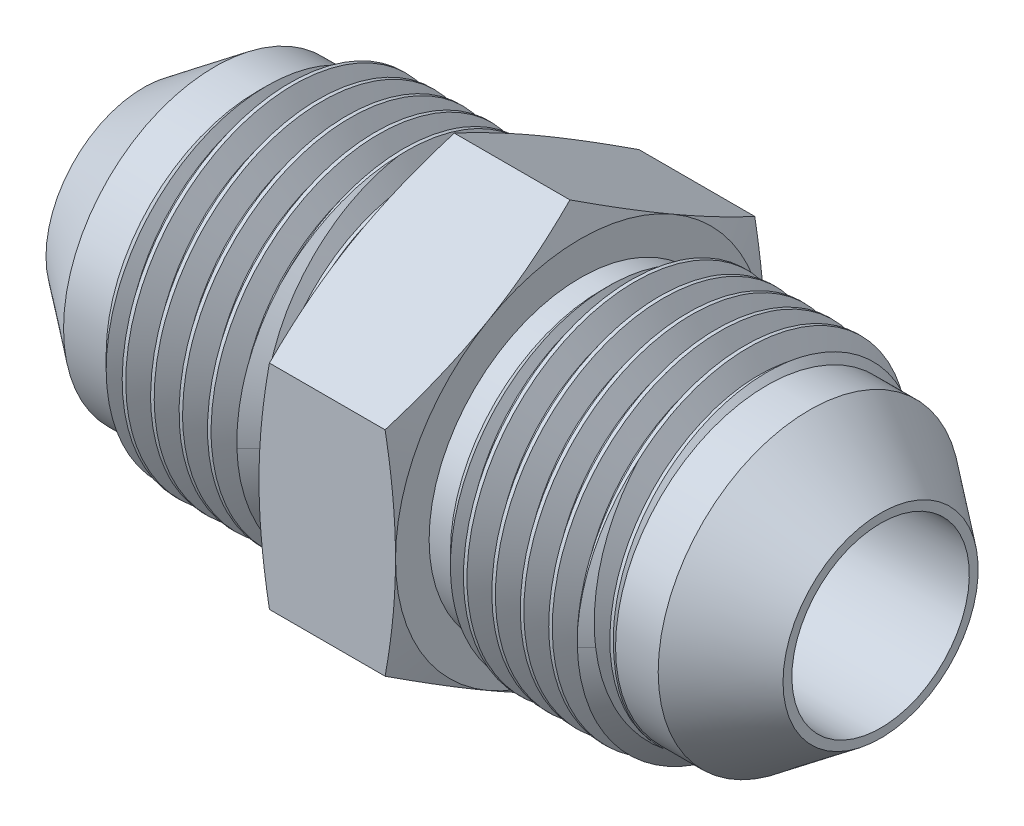
SolidWorks part; units mm, degrees
material "AISI 316 Annealed Stainless Steel Bar (SS)"
ref_plane "Front" through (0, 0, 0) normal (0, 0, 1) x (1, 0, 0)
ref_plane "Top" through (0, 0, 0) normal (0, 1, 0) x (1, 0, 0)
ref_plane "Right" through (0, 0, 0) normal (1, 0, 0) x (0, 0, -1)
sketch "Sketch6" plane through (0, 0, 0) normal (0, 0, 1) x (1, 0, 0)
  line L1 (20.574, 9.525) -> (20.574, -9.525) construction
  line L2 (-20.574, 0) -> (20.574, 0)
  line L4 (-20.574, 0) -> (-20.574, 9.525)
  line L5 (-20.574, 9.525) -> (20.574, 9.525)
  line L6 (20.574, 0) -> (20.574, 9.525)
  point P4 (3.81, 0)
  point P6 (-3.81, 0)
  dimension "Straight Dia" = 19.05
  dimension "Length" = 41.148
  dimension "L1" = 16.764
  dimension "D1" = 16.764
revolve "Revolve3" add sketch "Sketch6" angle 360 about L2
sketch "Sketch14" plane through (-20.574, 0, 0) normal (-1, 0, 0) x (0, 0, 1)
  circle A0 centre (0, 0) radius 9.525
  circle A2 centre (0, 0) radius 9.525 construction
curve "Helix/Spiral1" pitch 1.5875 height 42.7355 radius 9.525 centre (-20.574, 0, 0) axis (1, 0, 0) start towards (0, 1, 0) parameters "Pitch"=1.5875
sketch "Sketch15" plane through (0, 0, 0) normal (0, 0, 1) x (1, 0, 0)
  line L0 (-21.9631, 9.525) -> (-20.574, 9.525)
  line L1 (-20.574, 9.525) -> (-21.1693, 8.4939)
  line L2 (-21.1693, 8.4939) -> (-21.3678, 8.4939)
  line L3 (-21.3678, 8.4939) -> (-21.9631, 9.525)
  line L4 (-21.2685, 8.4939) -> (-21.2685, 9.525) construction
  line L5 (-21.6654, 9.0094) -> (-20.8717, 9.0094) construction
  dimension "D1" = 60
  dimension "D2" = 0.1984
  dimension "D3" = 0.7937
sweep "Cut-Sweep1" cut profiles "Sketch15" path "Helix/Spiral1" align with end faces yes
ref_plane "Plane1" through (-3.81, 0, 0) normal (1, 0, 0) x (0, 0, -1)
sketch "Sketch12" plane through (-3.81, 0, 0) normal (1, 0, 0) x (0, 0, -1)
  line L1 (0, 11.9151) -> (-10.3188, 5.9575)
  line L2 (-10.3188, 5.9575) -> (-10.3188, -5.9575)
  line L3 (-10.3188, -5.9575) -> (0, -11.9151)
  line L4 (0, -11.9151) -> (10.3188, -5.9575)
  line L5 (10.3188, -5.9575) -> (10.3188, 5.9575)
  line L6 (10.3188, 5.9575) -> (0, 11.9151)
  circle A0 centre (0, 0) radius 10.3187 construction
  dimension "Hex" = 20.6375
extrude "Extrude1" add sketch "Sketch12" along normal up to vertex (7.62 mm away) up to point (3.81, 0, 0)
sketch "Sketch7" plane through (0, 0, 0) normal (0, 0, 1) x (1, 0, 0)
  line L0 (-20.574, 0) -> (-20.574, 4.953)
  line L2 (-20.574, 4.953) -> (20.574, 4.953)
  line L4 (20.574, 0) -> (20.574, 9.525) construction
  line L11 (20.574, 4.953) -> (20.574, 0)
  line L12 (20.574, 0) -> (-20.574, 0)
  line L13 (-20.574, 4.953) -> (-20.574, -4.953) construction
  dimension "ID" = 9.906
revolve "Cut-Revolve5" cut sketch "Sketch7" angle 360 about L12
sketch "Sketch10" plane through (0, 0, 0) normal (0, 0, 1) x (1, 0, 0)
  line L0 (-20.574, 9.525) -> (-20.574, 5.4483)
  line L2 (-20.574, 5.4483) -> (-16.5998, 8.4431)
  line L3 (-16.5998, 8.4431) -> (-14.2185, 8.4431)
  line L4 (-14.2185, 8.4431) -> (-13.1366, 9.525)
  line L5 (-13.1366, 9.525) -> (-20.574, 9.525)
  line L6 (-6.0825, 9.525) -> (-3.81, 9.525)
  line L8 (-3.81, 9.525) -> (-3.81, 8.4431)
  line L9 (-3.81, 8.4431) -> (-5.0006, 8.4431)
  line L11 (-5.0006, 8.4431) -> (-6.0825, 9.525)
  line L13 (-20.574, 5.4483) -> (-20.574, -5.4483) construction
  line L14 (-20.574, 0) -> (0, 0) construction
  line L15 (-20.574, 0) -> (20.574, 0) construction
  line L16 (-3.81, 11.9151) -> (-3.81, 5.9575) construction
  line L17 (-20.574, 9.525) -> (20.574, 9.525) construction
  line L18 (0, 0) -> (0, 11.9151) construction
  line L19 (3.81, 11.9151) -> (-3.81, 11.9151) construction
  line L20 (5.0006, 8.4431) -> (6.0825, 9.525)
  line L21 (3.81, 8.4431) -> (5.0006, 8.4431)
  line L22 (3.81, 9.525) -> (3.81, 8.4431)
  line L23 (6.0825, 9.525) -> (3.81, 9.525)
  line L24 (13.1366, 9.525) -> (20.574, 9.525)
  line L25 (14.2185, 8.4431) -> (13.1366, 9.525)
  line L26 (16.5998, 8.4431) -> (14.2185, 8.4431)
  line L27 (20.574, 5.4483) -> (16.5998, 8.4431)
  line L28 (20.574, 9.525) -> (20.574, 5.4483)
  line L29 (-11.8428, -9.525) -> (-11.8428, 9.525) construction
  line L30 (0, 0) -> (-11.8428, 0) construction
  point P38 (-11.8428, -9.525)
  dimension "D1" = 45
  dimension "D2" = 1.1906
  dimension "D3" = 45
  dimension "D4" = 37
  dimension "D5" = 10.8966
  dimension "D6" = 2.3813
  dimension "D7" = 0.0508
  dimension "D8" = 8.7312
revolve "Cut-Revolve6" cut sketch "Sketch10" angle 360 about L2
sketch "Sketch16" plane through (-3.81, 0, 0) normal (-1, 0, 0) x (0, 0, 1)
  circle A0 centre (0, 0) radius 10.3187 construction
  circle A1 centre (0, 0) radius 10.3187
extrude "Cut-Extrude1" cut sketch "Sketch16" against normal through all draft 70 flip side to cut
sketch "Sketch17" plane through (3.81, 0, 0) normal (1, 0, 0) x (0, 0, -1)
  circle A1 centre (0, 0) radius 10.3187
  circle A2 centre (0, 0) radius 10.3187
  dimension "D1" = 0
extrude "Cut-Extrude2" cut sketch "Sketch17" against normal through all draft 70 flip side to cut
equation "\"D1@Sketch6\" = \"L1@Sketch6\""
equation "\"D2@Sketch15\" = \"Pitch@Helix/Spiral1\"*.125"
equation "\"D3@Sketch15\" = \"Pitch@Helix/Spiral1\"*.50"
equation "\"D3@Helix/Spiral1\" = \"Length@Sketch6\"+\"Pitch@Helix/Spiral1\""
equation "\"D2@Sketch10\" = \"Pitch@Helix/Spiral1\"*.750"
equation "\"D5@Sketch10\" = \"ID@Sketch7\"*1.1"
equation "\"D6@Sketch10\" = \"Pitch@Helix/Spiral1\"*1.50"
equation "\"D8@Sketch10\" = \"Pitch@Helix/Spiral1\"*5.50"
